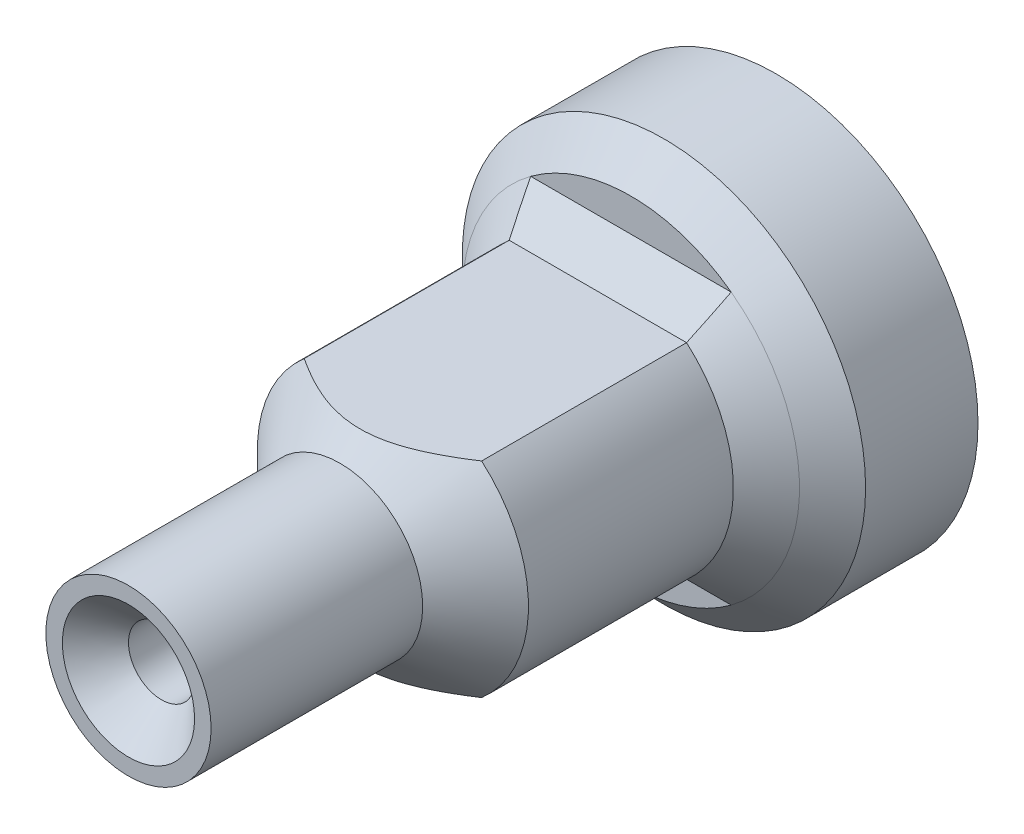
SolidWorks part; units mm, degrees
ref_plane "Plan de face" through (0, 0, 0) normal (0, 0, 1) x (1, 0, 0)
ref_plane "Plan de dessus" through (0, 0, 0) normal (0, 1, 0) x (1, 0, 0)
ref_plane "Plan de droite" through (0, 0, 0) normal (1, 0, 0) x (0, 0, -1)
sketch "Esquisse1" plane through (0, 0, 0) normal (0, 0, 1) x (1, 0, 0)
  circle A0 centre (0, 0) radius 4.6
  circle A1 centre (0, 0) radius 6.1
  dimension "D1" = 9.2
  dimension "D2" = 1.5
extrude "Boss.-Extru.1" add sketch "Esquisse1" along normal blind 1.7 contours A1 A0 region at (-5.9275, 0, 0)
sketch "Esquisse2" plane through (0, 0, 1.7) normal (0, 0, 1) x (1, 0, 0)
  circle A0 centre (0, 0) radius 2.6
  circle A1 centre (0, 0) radius 6.1
  circle A2 centre (0, 0) radius 6.1 construction
  dimension "D1" = 5.2
extrude "Boss.-Extru.2" add sketch "Esquisse2" along normal blind 2.7 contours A0 | A1 region at (0, 0, 1.7)
sketch "Esquisse3" plane through (0, 0, 4.4) normal (0, 0, 1) x (1, 0, 0)
  line L1 (-2.0494, -1.6) -> (2.0494, -1.6)
  line L2 (-2.0494, -1.6) -> (-2.0494, 1.6) construction
  line L3 (-2.0494, 1.6) -> (2.0494, 1.6)
  line L4 (2.0494, -1.6) -> (2.0494, 1.6) construction
  line L5 (-2.6833, 3.1) -> (2.6833, 3.1)
  line L6 (-2.6833, 3.1) -> (-2.6833, -3.1) construction
  line L7 (-2.6833, -3.1) -> (2.6833, -3.1)
  line L8 (2.6833, 3.1) -> (2.6833, -3.1) construction
  line L9 (-2.6833, 3.1) -> (2.6833, -3.1) construction
  line L10 (-2.6833, -3.1) -> (2.6833, 3.1) construction
  circle A0 centre (0, 0) radius 2.6
  circle A1 centre (0, 0) radius 2.6 construction
  circle A2 centre (0, 0) radius 4.1
  point P7 (0, 0)
  circle M12 centre (0, 0) radius 2.6
  dimension "D2" = 1.5
  dimension "D1" = 3.2
  dimension "D3" = 1.5
extrude "Boss.-Extru.3" add sketch "Esquisse3" along normal blind 6.2 contours L5 A2 L7 M12 | L3 M12 | L1 M12 region at (0, -2.0074, 4.4) region at (0, 2.0074, 4.4) region at (0, 2.9972, 4.4)
sketch "Esquisse4" plane through (0, 0, 10.6) normal (0, 0, 1) x (1, 0, 0)
  line L1 (-2.6833, -3.1) -> (2.6833, -3.1)
  line L2 (-2.6833, -3.1) -> (-2.6833, 3.1)
  line L3 (-2.6833, 3.1) -> (2.6833, 3.1)
  line L4 (2.6833, -3.1) -> (2.6833, 3.1)
  line L5 (-2.6833, -3.1) -> (2.6833, 3.1) construction
  line L6 (-2.6833, 3.1) -> (2.6833, -3.1) construction
  circle A0 centre (0, 0) radius 4.1
  arc M11 (-2.6833, 3.1) -> (-2.6833, -3.1) centre (0, 0) ccw
  arc M13 (2.6833, -3.1) -> (2.6833, 3.1) centre (0, 0) ccw
extrude "Boss.-Extru.4" add sketch "Esquisse4" along normal blind 1 contours L2 M11 | L4 M13 | L3 L4 L1 L2 region at (-3.2593, 0, 10.6) region at (3.2593, 0, 10.6)
chamfer "Chanfrein1" distance 1 angle 45 5 edges at (6.1, 0, 4.4) (4.1, 0, 4.4) (0, -3.1, 4.4) (0, 3.1, 4.4) (-4.1, 0, 4.4)
chamfer "Chanfrein2" distance 1 angle 45 2 edges at (0, -1.6, 4.4) (0, 1.6, 4.4)
sketch "Esquisse5" plane through (0, 0, 11.6) normal (0, 0, 1) x (1, 0, 0)
  circle A0 centre (0, 0) radius 1
  circle A1 centre (0, 0) radius 2.5
  dimension "D1" = 2
  dimension "D2" = 1.5
extrude "Boss.-Extru.5" add sketch "Esquisse5" along normal blind 8 contours A1 A0 region at (-2.4293, 0, 11.6)
chamfer "Chanfrein3" distance 1 angle 45 1 edges at (1, 0, 19.6)
chamfer "Chanfrein4" distance 1.6 angle 45 1 edges at (2.5, 0, 11.6)
